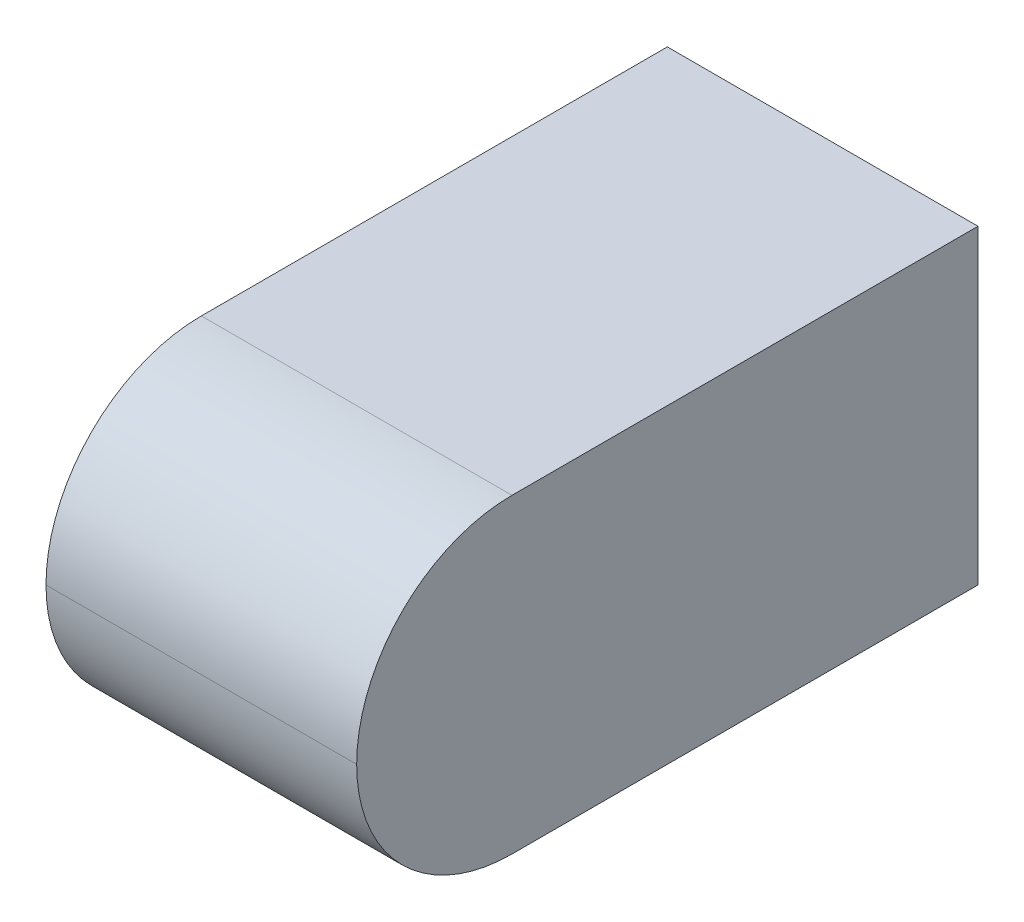
SolidWorks part; units mm, degrees
ref_plane "正面" through (0, 0, 0) normal (0, 0, 1) x (1, 0, 0)
ref_plane "平面" through (0, 0, 0) normal (0, 1, 0) x (1, 0, 0)
ref_plane "右側面" through (0, 0, 0) normal (1, 0, 0) x (0, 0, -1)
sketch "ｽｹｯﾁ1" plane through (0, 0, 0) normal (0, 0, 1) x (1, 0, 0)
  line L1 (-7.5, -7.5) -> (7.5, -7.5)
  line L2 (-7.5, -7.5) -> (-7.5, 7.5)
  line L3 (-7.5, 7.5) -> (7.5, 7.5)
  line L4 (7.5, -7.5) -> (7.5, 7.5)
  line L5 (-7.5, -7.5) -> (7.5, 7.5) construction
  line L6 (-7.5, 7.5) -> (7.5, -7.5) construction
  circle A0 centre (0, 0) radius 5.5
  dimension "D1" = 11
  dimension "D3" = 15
  dimension "D4" = 15
extrude "ﾎﾞｽ - 押し出し1" add sketch "ｽｹｯﾁ1" along normal blind 30
sketch "ｽｹｯﾁ5" plane through (0, 0, 30) normal (0, 0, 1) x (1, 0, 0)
  line L1 (7.5, -7.5) -> (-7.5, -7.5)
  line L2 (7.5, -7.5) -> (7.5, 7.5)
  line L3 (7.5, 7.5) -> (-7.5, 7.5)
  line L4 (-7.5, -7.5) -> (-7.5, 7.5)
  line L5 (7.5, -7.5) -> (-7.5, 7.5) construction
  line L6 (7.5, 7.5) -> (-7.5, -7.5) construction
  point P0 (0, 0)
extrude "ﾎﾞｽ - 押し出し3" add sketch "ｽｹｯﾁ5" against normal blind 20
fillet "ﾌｨﾚｯﾄ2" radius 7.5 2 edges at (0, -7.5, 30) (0, 7.5, 30)
